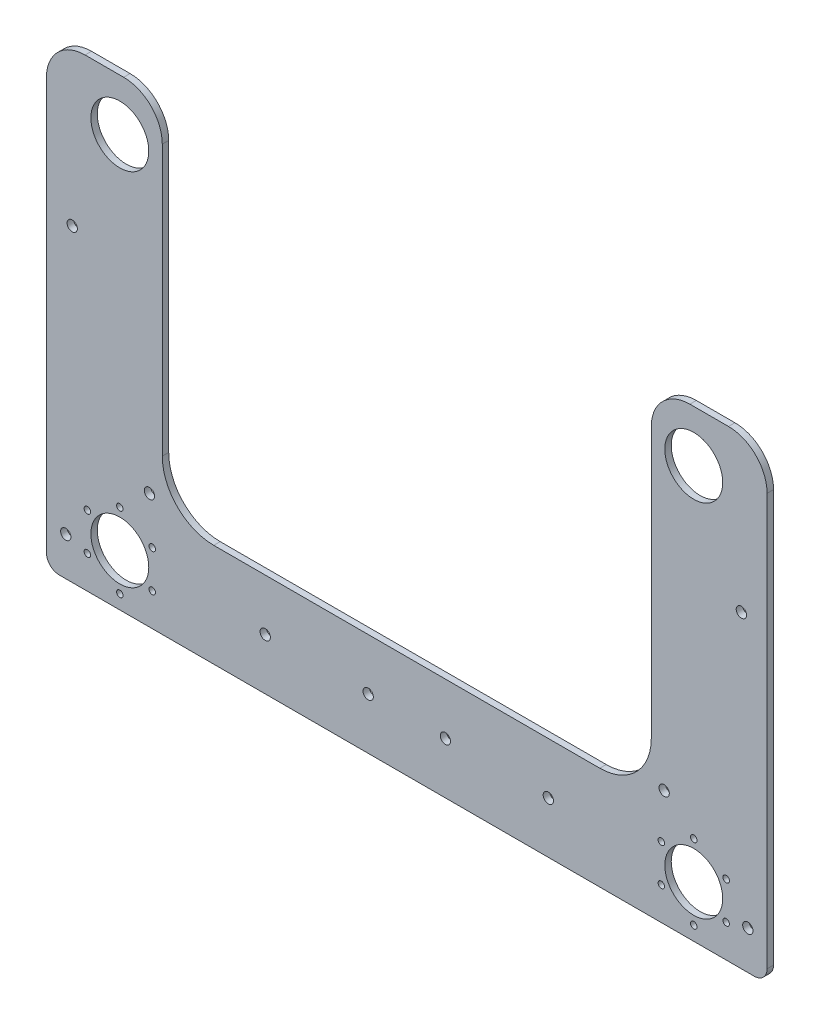
SolidWorks part; units mm, degrees
material "6061 Alloy"
ref_plane "Front Plane" through (0, 0, 0) normal (0, 0, 1) x (1, 0, 0)
ref_plane "Top Plane" through (0, 0, 0) normal (0, 1, 0) x (1, 0, 0)
ref_plane "Right Plane" through (0, 0, 0) normal (1, 0, 0) x (0, 0, -1)
sketch "Sketch1" plane through (0, 0, 0) normal (0, 0, 1) x (1, 0, 0)
  line L5 (120.65, -152.4) -> (120.65, -6.35)
  line L6 (127, 0) -> (171.45, 0) construction
  line L7 (177.8, -6.35) -> (177.8, -222.25)
  line L10 (0, -206.2199) -> (0, -63.6275) construction
  line L11 (-54.9244, 0) -> (300.6756, 0) construction
  line L13 (12.7, -177.8) -> (95.25, -177.8)
  line L14 (12.7, -228.6) -> (171.45, -228.6)
  line L15 (141.605, -25.4) -> (141.605, -84.2822) construction
  line L16 (141.605, -25.4) -> (141.605, -127) construction
  line L17 (-141.605, -25.4) -> (-141.605, -203.2) construction
  line L18 (-141.605, -25.4) -> (-141.605, -127) construction
  line L19 (-141.605, -19.05) -> (-141.605, -77.9322) construction
  line L20 (141.605, -25.4) -> (141.605, -203.2) construction
  line L22 (-120.65, -152.4) -> (-120.65, -6.35)
  line L23 (-12.7, -177.8) -> (-95.25, -177.8)
  line L24 (-12.7, -228.6) -> (-171.45, -228.6)
  line L25 (-177.8, -6.35) -> (-177.8, -222.25)
  line L26 (-12.7, -177.8) -> (12.7, -177.8)
  line L27 (-12.7, -228.6) -> (12.7, -228.6)
  line L28 (-177.8, -6.35) -> (-177.8, 6.35)
  line L29 (-165.1, 19.05) -> (-133.35, 19.05)
  line L30 (-120.65, 6.35) -> (-120.65, -6.35)
  line L31 (120.65, 6.35) -> (120.65, -6.35)
  line L32 (177.8, -6.35) -> (177.8, 6.35)
  line L33 (165.1, 19.05) -> (133.35, 19.05)
  arc A0 (95.25, -177.8) -> (120.65, -152.4) centre (95.25, -152.4) ccw
  arc A4 (120.65, -6.35) -> (127, 0) centre (127, -6.35) cw construction
  circle A8 centre (141.605, -25.4) radius 14.2875
  circle A9 centre (141.605, -25.4) radius 38.1 construction
  arc A10 (177.8, -6.35) -> (171.45, 0) centre (171.45, -6.35) ccw construction
  arc A11 (171.45, -228.6) -> (177.8, -222.25) centre (171.45, -222.25) ccw
  arc A14 (141.605, -82.55) -> (120.9214, -78.6758) centre (141.605, -25.4) ccw construction
  arc A15 (-141.605, -82.55) -> (-120.9214, -78.6758) centre (-141.605, -25.4) cw construction
  circle A16 centre (-141.605, -25.4) radius 38.1 construction
  circle A17 centre (-141.605, -25.4) radius 14.2875
  arc A19 (-95.25, -177.8) -> (-120.65, -152.4) centre (-95.25, -152.4) cw
  circle A20 centre (141.605, -127) radius 38.1 construction
  circle A21 centre (-141.605, -127) radius 38.1 construction
  arc A23 (-171.45, -228.6) -> (-177.8, -222.25) centre (-171.45, -222.25) cw
  circle A24 centre (-141.605, -203.2) radius 14.2875
  circle A25 centre (-141.605, -184.7225) radius 1.6002
  circle A26 centre (-125.603, -193.9612) radius 1.6002
  circle A27 centre (-125.603, -212.4388) radius 1.6002
  circle A28 centre (-141.605, -221.6775) radius 1.6002
  circle A29 centre (-157.607, -212.4388) radius 1.6002
  circle A30 centre (-157.607, -193.9612) radius 1.6002
  circle A31 centre (157.607, -212.4388) radius 1.6002
  circle A32 centre (157.607, -193.9612) radius 1.6002
  circle A33 centre (141.605, -184.7225) radius 1.6002
  circle A34 centre (125.603, -193.9612) radius 1.6002
  circle A35 centre (125.603, -212.4388) radius 1.6002
  circle A36 centre (141.605, -221.6775) radius 1.6002
  circle A37 centre (141.605, -203.2) radius 14.2875
  circle A39 centre (-69.85, -203.2) radius 2.54
  circle A40 centre (69.85, -203.2) radius 2.54
  circle A42 centre (-19.05, -203.2) radius 2.54
  circle A43 centre (-127, -171.45) radius 2.54
  arc A44 (-133.35, 19.05) -> (-120.65, 6.35) centre (-133.35, 6.35) cw
  arc A45 (-177.8, 6.35) -> (-165.1, 19.05) centre (-165.1, 6.35) cw
  arc A46 (133.35, 19.05) -> (120.65, 6.35) centre (133.35, 6.35) ccw
  arc A47 (177.8, 6.35) -> (165.1, 19.05) centre (165.1, 6.35) ccw
  circle A50 centre (-149.225, 6.35) radius 2.54
  circle A51 centre (127, -171.45) radius 2.54
  circle A53 centre (149.225, 6.35) radius 2.54
  circle A54 centre (-168.275, -209.55) radius 2.54
  circle A56 centre (168.275, -209.55) radius 2.54
  circle A58 centre (-165.1, -76.2) radius 2.54
  circle A59 centre (165.1, -76.2) radius 2.54
  circle A60 centre (19.05, -203.2) radius 2.54
  point P2 (177.8, -44.45)
  point P18 (177.8, 0)
  point P23 (177.8, -228.6)
  point P24 (177.8, -228.6)
  point P31 (177.8, 0)
  point P48 (-177.8, 0)
  point P49 (-177.8, -228.6)
  point P51 (-177.8, -44.45)
  point P78 (-141.605, -203.2)
  dimension "D6" = 25.4
  dimension "D7" = 6.35
  dimension "D8" = 6.35
  dimension "D9" = 177.8
  dimension "D10" = 28.575
  dimension "D12" = 76.2
  dimension "D13" = 57.15
  dimension "D15" = 28.575
  dimension "D18" = 76.2
  dimension "D21" = 3.2004
  dimension "D29" = 9.525
  dimension "D32" = 5.08
  dimension "D35" = 5.08
  dimension "D37" = 5.08
  dimension "D40" = 12.7
  dimension "D43" = 5.08
  dimension "D45" = 12.7
  dimension "D30" = 5.08
  dimension "D41" = 5.08
  dimension "D2" = 120.65
  dimension "D3" = 177.8
  dimension "D4" = 228.6
  dimension "D5" = 177.8
  dimension "D11" = 20.955
  dimension "`" = 25.4
  dimension "D14" = 57.15
  dimension "D16" = 184.15
  dimension "D17" = 101.6
  dimension "D19" = 25.4
  dimension "D20" = 107.95
  dimension "D22" = 0
  dimension "D23" = 18.4775
  dimension "D25" = 6.9225
  dimension "D26" = 19.05
  dimension "D27" = 25.4
  dimension "D28" = 25.4
  dimension "D31" = 95.25
  dimension "D33" = 12.7
  dimension "D34" = 25.4
  dimension "D38" = 57.15
  dimension "D39" = 19.05
  dimension "D42" = 6.35
  dimension "D44" = 28.575
  dimension "D46" = 19.05
  dimension "D24" = 6
extrude "Boss-Extrude3" add sketch "Sketch1" along normal blind 3.175
sketch "Sketch2" plane through (0, 0, 3.175) normal (0, 0, 1) x (1, 0, 0)
  line L0 (-133.35, 19.05) -> (-165.1, 19.05) construction
  line L1 (-177.8, 19.05) -> (177.8, 19.05)
  line L2 (-177.8, 19.05) -> (-177.8, 0)
  line L3 (-177.8, 0) -> (177.8, 0)
  line L4 (177.8, 19.05) -> (177.8, 0)
  line L5 (-177.8, 6.35) -> (-177.8, -222.25) construction
  line L6 (177.8, -222.25) -> (177.8, 6.35) construction
  dimension "D1" = 19.05
extrude "Cut-Extrude1" cut sketch "Sketch2" against normal through all
fillet "Fillet1" radius 19.05 4 edges at (177.8, 0, 1.5875) (120.65, 0, 1.5875) (-120.65, 0, 1.5875) (-177.8, 0, 1.5875)
